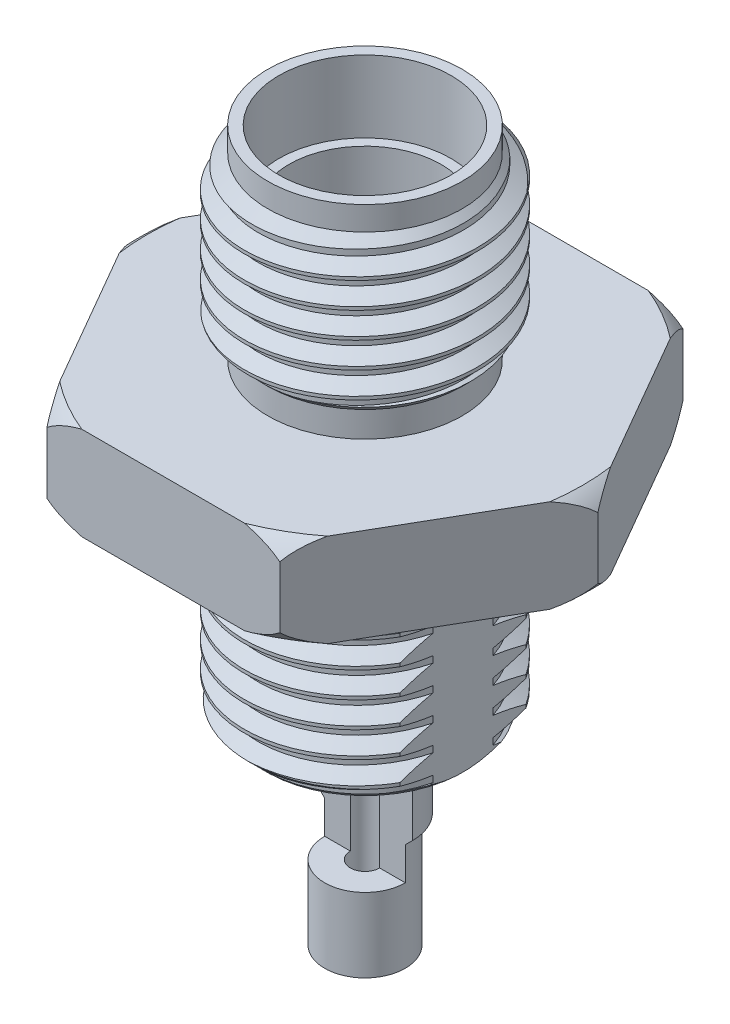
SolidWorks part; units mm, degrees
material "Brass"
ref_plane "Ön Düzlem" through (0, 0, 0) normal (0, 0, 1) x (1, 0, 0)
ref_plane "Üst Düzlem" through (0, 0, 0) normal (0, 1, 0) x (1, 0, 0)
ref_plane "Sağ Düzlem" through (0, 0, 0) normal (1, 0, 0) x (0, 0, -1)
ref_axis "Axis1" through (0, 0, 0) along (0, 1, 0)
sketch "Sketch1" plane through (0, 0, 0) normal (0, 0, 1) x (1, 0, 0)
  line L0 (-0.4, 0) -> (-0.4, 6.4)
  line L1 (-0.4, 6.4) -> (-2.075, 6.4)
  line L2 (-0.4, 0) -> (-1.1, 0)
  line L3 (-1.1, 0) -> (-1.1, 2.92)
  line L4 (-1.1, 2.92) -> (-1.3, 3.12)
  line L5 (-1.3, 3.12) -> (-1.3, 5.42)
  line L6 (-1.3, 5.42) -> (-2.675, 5.42)
  line L7 (-2.675, 5.42) -> (-3.175, 5.92)
  line L8 (-3.175, 5.92) -> (-3.175, 12.33)
  line L9 (-3.175, 12.33) -> (-4.775, 12.33)
  line L10 (-4.775, 12.33) -> (-4.775, 11.28)
  line L11 (-4.775, 11.28) -> (-6.35, 11.28)
  line L12 (-6.35, 11.28) -> (-6.35, 13.82)
  line L13 (-6.35, 13.82) -> (-2.65, 13.82)
  line L14 (-2.65, 13.82) -> (-2.65, 14.52)
  line L15 (-2.65, 19.36) -> (-2.35, 19.36)
  line L16 (-2.35, 19.36) -> (-2.35, 17.4)
  line L17 (-2.35, 17.4) -> (-2.075, 17.4)
  line L18 (-2.075, 17.4) -> (-2.075, 6.4)
  line L19 (-2.65, 14.52) -> (-3.175, 15.045)
  line L20 (-3.175, 15.045) -> (-3.175, 18.185)
  line L21 (-3.175, 18.185) -> (-2.65, 18.71)
  line L22 (-2.65, 18.71) -> (-2.65, 19.36)
  dimension "D1" = 1.1
  dimension "D2" = 0.4
  dimension "D3" = 2.92
  dimension "D4" = 3.12
  dimension "D5" = 1.3
  dimension "D6" = 5.42
  dimension "D7" = 3.175
  dimension "D8" = 2.675
  dimension "D9" = 12.33
  dimension "D10" = 11.28
  dimension "D11" = 6.35
  dimension "D12" = 4.775
  dimension "D13" = 13.82
  dimension "D14" = 2.65
  dimension "D15" = 2.35
  dimension "D16" = 19.36
  dimension "D17" = 17.4
  dimension "D18" = 2.075
  dimension "D19" = 6.4
  dimension "D20" = 18.71
  dimension "D21" = 45
  dimension "D22" = 45
  dimension "D23" = 14.52
revolve "Revolve1" add sketch "Sketch1" angle 360 about axis through (0, 0, 0) along (0, 1, 0)
sketch "Sketch2" plane through (0, 0, 0) normal (0, 1, 0) x (1, 0, 0)
  line L1 (-3.175, 5.4993) -> (-6.35, 0)
  line L2 (-6.35, 0) -> (-3.175, -5.4993)
  line L3 (-3.175, -5.4993) -> (3.175, -5.4993)
  line L4 (3.175, -5.4993) -> (6.35, 0)
  line L5 (6.35, 0) -> (3.175, 5.4993)
  line L6 (3.175, 5.4993) -> (-3.175, 5.4993)
  circle A0 centre (0, 0) radius 5.4993 construction
  circle A1 centre (0, 0) radius 6.35 construction
extrude "Cut-Extrude1" cut sketch "Sketch2" along normal through all flip side to cut
sketch "Sketch4" plane through (0, 0, 0) normal (0, 0, 1) x (1, 0, 0)
  line L0 (-6.35, 11.7119) -> (-6.35, 13.3881)
  line L1 (-5.9306, 13.82) -> (-5.9306, 14.55)
  line L2 (-5.9306, 14.55) -> (-7.9306, 14.55)
  line L3 (-7.9306, 14.55) -> (-7.9306, 10.55)
  line L4 (-7.9306, 10.55) -> (-5.9306, 10.55)
  line L5 (-5.9306, 10.55) -> (-5.9306, 11.28)
  line L6 (-6.35, 13.82) -> (-6.35, 11.28) construction
  line L7 (-3.175, 13.82) -> (-6.35, 13.82) construction
  arc A1 (-5.9306, 13.82) -> (-6.35, 13.3881) centre (-5.1267, 12.6199) ccw
  arc A3 (-6.35, 11.7119) -> (-5.9306, 11.28) centre (-5.1267, 12.4801) ccw
  point P7 (-6.35, 12.55)
  dimension "D4" = 1.4445
  dimension "D5" = 1.4445
  dimension "D1" = 2
  dimension "D2" = 2
  dimension "D3" = 4
  dimension "D6" = 0.4194
  dimension "D7" = 0.73
  dimension "D8" = 1.6761
revolve "Cut-Revolve1" cut sketch "Sketch4" angle 360 about axis through (0, 0, 0) along (0, 1, 0)
thread "Thread1" pitch 0.7056 method cut profile "Thread Profile1" start angle 120, offset 1, length 5.84, pitch 0.7056, diameter 6.35
ref_plane "Plane1" through (-1.5875, 4.92, -2.7496) normal (0.866, 0, -0.5) x (-0.5, 0, -0.866)
sketch "Thread Profile1" plane through (-1.5875, 4.92, -2.7496) normal (0.866, 0, -0.5) x (-0.5, 0, -0.866)
  line L0 (0, 0) -> (0, 0.7056) construction
  line L11 (0, 0) -> (0, 0.6174)
  line L12 (0, 0.6174) -> (-0.3819, 0.3969)
  line L13 (-0.3819, 0.3969) -> (-0.3819, 0.2205)
  line L15 (-0.3819, 0.2205) -> (0, 0)
  line L17 (-0.3819, 0.3087) -> (0, 0.3087) construction
  point P2 (0, 0)
  dimension "Pitch" = 0.7056
  dimension "Profile_Angle" = 60
  dimension "Profile_Land" = 0.1764
  dimension "Profile_Height" = 0.3819
thread "Thread2" pitch 0.7056 method cut profile "Thread Profile2" start angle 310, offset 1, length 4.5, pitch 0.7056, diameter 6.35
ref_plane "Plane2" through (-2.0409, 19.185, 2.4322) normal (0.766, 0, 0.6428) x (-0.6428, 0, 0.766)
sketch "Thread Profile2" plane through (-2.0409, 19.185, 2.4322) normal (0.766, 0, 0.6428) x (-0.6428, 0, 0.766)
  line L0 (0, 0) -> (0, 0.7056) construction
  line L11 (0, 0) -> (0, 0.6174)
  line L12 (0, 0.6174) -> (-0.3819, 0.3969)
  line L13 (-0.3819, 0.3969) -> (-0.3819, 0.2205)
  line L15 (-0.3819, 0.2205) -> (0, 0)
  line L17 (-0.3819, 0.3087) -> (0, 0.3087) construction
  point P2 (0, 0)
  dimension "Pitch" = 0.7056
  dimension "Profile_Angle" = 60
  dimension "Profile_Land" = 0.1764
  dimension "Profile_Height" = 0.3819
sketch "Sketch20" plane through (0, 0, 0) normal (1, 0, 0) x (0, 0, -1)
  line L1 (0, 2.02) -> (-2, 2.02)
  line L2 (0, 2.02) -> (0, 4.62)
  line L3 (0, 4.62) -> (-2, 4.62)
  line L4 (-2, 2.02) -> (-2, 4.62)
  dimension "D1" = 2.02
  dimension "D2" = 2
  dimension "D3" = 2.6
extrude "Cut-Extrude3" cut sketch "Sketch20" against normal through all both and the other way through all
sketch "Sketch21" plane through (0, 0, 0) normal (0, 0, 1) x (1, 0, 0)
  line L0 (3.6523, 11.28) -> (5.8727, 11.28) construction
  line L1 (6.35, 11.28) -> (2.67, 11.28)
  line L2 (6.35, 11.28) -> (6.35, 0)
  line L3 (6.35, 0) -> (2.67, 0)
  line L4 (2.67, 11.28) -> (2.67, 0)
  line L5 (6.35, 13.3881) -> (6.35, 11.7119) construction
  dimension "D1" = 3.68
extrude "Cut-Extrude4" cut sketch "Sketch21" against normal through all both and the other way through all
